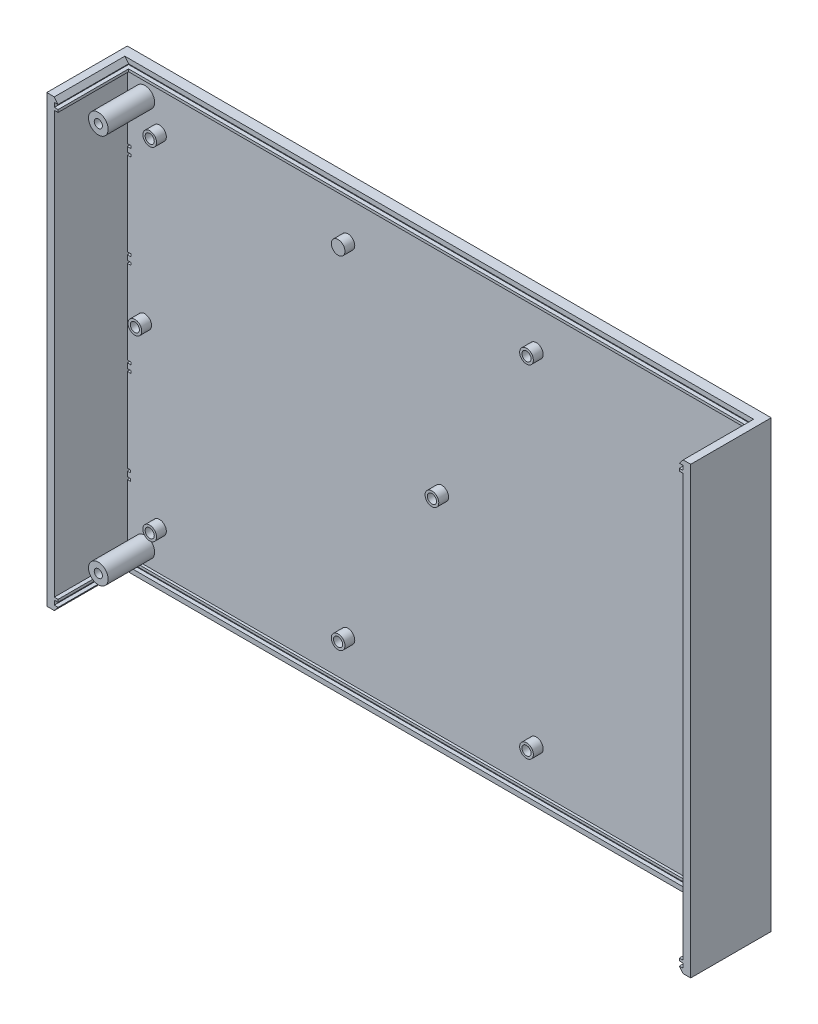
SolidWorks part; units mm, degrees
ref_plane "Front Plane" through (0, 0, 0) normal (0, 0, 1) x (1, 0, 0)
ref_plane "Top Plane" through (0, 0, 0) normal (0, 1, 0) x (1, 0, 0)
ref_plane "Right Plane" through (0, 0, 0) normal (1, 0, 0) x (0, 0, -1)
sketch "Sketch1" plane through (0, 0, 0) normal (0, 0, 1) x (1, 0, 0)
  line L0 (-127, 85.1535) -> (-127, -87.9475)
  line L81 (127, 85.1535) -> (127, -85.1535)
  line L83 (130.048, -89.8525) -> (130.048, 89.8525)
  line L86 (-127, 87.9475) -> (-127, 86.1695)
  line L87 (-130.048, 89.8525) -> (-130.048, -89.8525)
  line L88 (-127, -87.9475) -> (77.8375, -87.9475)
  line L89 (-127, -86.1695) -> (78.8702, -86.1695)
  line L90 (-127, -85.1535) -> (79.4604, -85.1535)
  line L91 (-130.048, -89.8525) -> (130.048, -89.8525)
  line L93 (-119.7257, 56.769) -> (-134.1956, 56.769) construction
  line L94 (-125.603, 58.7756) -> (-125.603, 57.7596)
  line L95 (-125.603, 54.7624) -> (-125.603, 55.7784)
  line L96 (-127, 58.7756) -> (-125.603, 58.7756)
  line L97 (-127, 57.7596) -> (-125.603, 57.7596)
  line L98 (-127, 55.7784) -> (-125.603, 55.7784)
  line L99 (-127, 54.7624) -> (-125.603, 54.7624)
  line L100 (127, -86.1695) -> (127, -87.9475)
  line L101 (77.8375, -87.9475) -> (127, -87.9475)
  line L102 (78.8702, -86.1695) -> (127, -86.1695)
  line L103 (79.4604, -85.1535) -> (127, -85.1535)
  line L104 (125.603, 58.7756) -> (125.603, 57.7596) construction
  line L105 (125.603, 54.7624) -> (125.603, 55.7784) construction
  line L106 (127, 58.7756) -> (125.603, 58.7756) construction
  line L107 (127, 57.7596) -> (125.603, 57.7596) construction
  line L108 (127, 55.7784) -> (125.603, 55.7784) construction
  line L109 (127, 54.7624) -> (125.603, 54.7624) construction
  line L110 (79.0715, 85.1535) -> (-127, 85.1535)
  line L111 (78.336, 86.1695) -> (-127, 86.1695)
  line L112 (77.0488, 87.9475) -> (-127, 87.9475)
  line L113 (130.048, 89.8525) -> (-130.048, 89.8525)
  line L115 (127, 87.9475) -> (77.0488, 87.9475)
  line L116 (127, 86.1695) -> (78.336, 86.1695)
  line L117 (127, 85.1535) -> (79.0715, 85.1535)
  line L118 (127, 87.9475) -> (127, 86.1695)
  line L119 (-119.7257, 18.923) -> (-134.1956, 18.923) construction
  line L120 (-125.603, 16.9164) -> (-125.603, 17.9324)
  line L121 (-127, 17.9324) -> (-125.603, 17.9324)
  line L122 (-127, 16.9164) -> (-125.603, 16.9164)
  line L123 (-127, 19.9136) -> (-125.603, 19.9136)
  line L124 (-127, 20.9296) -> (-125.603, 20.9296)
  line L125 (-125.603, 20.9296) -> (-125.603, 19.9136)
  line L126 (125.603, 16.9164) -> (125.603, 17.9324) construction
  line L127 (127, 17.9324) -> (125.603, 17.9324) construction
  line L128 (127, 16.9164) -> (125.603, 16.9164) construction
  line L129 (127, 19.9136) -> (125.603, 19.9136) construction
  line L130 (127, 20.9296) -> (125.603, 20.9296) construction
  line L131 (125.603, 20.9296) -> (125.603, 19.9136) construction
  line L132 (-119.7257, -18.923) -> (-134.1956, -18.923) construction
  line L133 (-125.603, -20.9296) -> (-125.603, -19.9136)
  line L134 (-127, -19.9136) -> (-125.603, -19.9136)
  line L135 (-127, -20.9296) -> (-125.603, -20.9296)
  line L136 (-127, -17.9324) -> (-125.603, -17.9324)
  line L137 (-127, -16.9164) -> (-125.603, -16.9164)
  line L138 (-125.603, -16.9164) -> (-125.603, -17.9324)
  line L139 (125.603, -20.9296) -> (125.603, -19.9136) construction
  line L140 (127, -19.9136) -> (125.603, -19.9136) construction
  line L141 (127, -20.9296) -> (125.603, -20.9296) construction
  line L142 (127, -17.9324) -> (125.603, -17.9324) construction
  line L143 (127, -16.9164) -> (125.603, -16.9164) construction
  line L144 (125.603, -16.9164) -> (125.603, -17.9324) construction
  line L145 (-119.7257, -56.769) -> (-134.1956, -56.769) construction
  line L146 (-125.6284, -58.7756) -> (-125.6284, -57.7596)
  line L147 (-127.0254, -57.7596) -> (-125.6284, -57.7596)
  line L148 (-127.0254, -58.7756) -> (-125.6284, -58.7756)
  line L149 (-127.0254, -55.7784) -> (-125.6284, -55.7784)
  line L150 (-127.0254, -54.7624) -> (-125.6284, -54.7624)
  line L151 (-125.6284, -54.7624) -> (-125.6284, -55.7784)
  line L152 (125.603, -58.7756) -> (125.603, -57.7596) construction
  line L153 (127, -57.7596) -> (125.603, -57.7596) construction
  line L154 (127, -58.7756) -> (125.603, -58.7756) construction
  line L155 (127, -55.7784) -> (125.603, -55.7784) construction
  line L156 (127, -54.7624) -> (125.603, -54.7624) construction
  line L157 (125.603, -54.7624) -> (125.603, -55.7784) construction
  line L158 (127, -89.8525) -> (125.476, -87.9475)
  line L159 (125.476, -86.1695) -> (125.476, -85.1535)
  line L160 (-127, -89.8525) -> (-125.476, -87.9475)
  line L161 (-125.476, -86.1695) -> (-125.476, -85.1535)
  line L162 (125.476, 86.1695) -> (125.476, 85.1535)
  line L163 (127, 89.8525) -> (125.476, 87.9475)
  line L164 (-127, 89.8525) -> (-125.476, 87.9475)
  line L165 (-125.476, 86.1695) -> (-125.476, 85.1535)
  circle A0 centre (-119.9134, -78.6765) radius 3.9624
  circle A1 centre (-113.9952, -68.9864) radius 2.7686
  circle A2 centre (-113.9952, -68.9864) radius 1.143
  circle A3 centre (-113.9952, -68.9864) radius 1.8415
  circle A4 centre (-119.9134, -78.6765) radius 1.651
  circle A5 centre (119.9134, -78.6765) radius 1.651 construction
  circle A6 centre (119.9134, -78.6765) radius 3.9624 construction
  circle A7 centre (-119.9134, 78.6765) radius 3.9624
  circle A8 centre (-119.9134, 78.6765) radius 1.651
  circle A9 centre (119.9134, 78.6765) radius 3.9624 construction
  circle A10 centre (119.9134, 78.6765) radius 1.651 construction
  circle A11 centre (0, 0) radius 2.7686
  circle A12 centre (0, 0) radius 1.8415
  circle A13 centre (0, 0) radius 1.143
  circle A14 centre (-113.9952, 68.9864) radius 1.8415
  circle A15 centre (-113.9952, 68.9864) radius 2.7686
  circle A16 centre (-113.9952, 68.9864) radius 1.143
  circle A17 centre (-37.8968, -68.9864) radius 1.8415
  circle A18 centre (-37.8968, -68.9864) radius 2.7686
  circle A19 centre (-37.8968, -68.9864) radius 1.143
  circle A20 centre (-37.8968, 68.9864) radius 2.7686
  circle A21 centre (-37.8968, 68.9864) radius 1.8415
  circle A22 centre (-37.8968, 68.9864) radius 1.143
  circle A23 centre (38.2016, -68.9864) radius 1.8415
  circle A24 centre (38.2016, -68.9864) radius 2.7686
  circle A25 centre (38.2016, -68.9864) radius 1.143
  circle A26 centre (38.2016, 68.9864) radius 2.7686
  circle A27 centre (38.2016, 68.9864) radius 1.8415
  circle A28 centre (38.2016, 68.9864) radius 1.143
  circle A29 centre (114.3, -68.9864) radius 1.8415 construction
  circle A30 centre (114.3, -68.9864) radius 2.7686 construction
  circle A31 centre (114.3, -68.9864) radius 1.143 construction
  circle A32 centre (114.3, 68.9864) radius 2.7686 construction
  circle A33 centre (114.3, 68.9864) radius 1.8415 construction
  circle A34 centre (114.3, 68.9864) radius 1.143 construction
  circle A35 centre (-119.9896, 0) radius 1.143
  circle A36 centre (-119.9896, 0) radius 1.8415
  circle A37 centre (-119.9896, 0) radius 2.7686
  circle A38 centre (119.9896, 0) radius 1.143 construction
  circle A39 centre (119.9896, 0) radius 1.8415 construction
  circle A40 centre (119.9896, 0) radius 2.7686 construction
  dimension "D1" = 2.286
  dimension "D2" = 3.683
  dimension "D3" = 5.5372
  dimension "D4" = 3.302
  dimension "D5" = 7.9248
  dimension "D6" = 38.2016
  dimension "D7" = 77.0488
  dimension "D8" = 77.8375
  dimension "D9" = 78.336
  dimension "D10" = 78.8702
  dimension "D11" = 79.0715
  dimension "D12" = 79.4604
  dimension "D13" = 114.3
  dimension "D14" = 119.9134
  dimension "D15" = 119.9896
  dimension "D16" = 125.476
  dimension "D17" = 125.603
  dimension "D18" = 127
  dimension "D19" = 85.1535
  dimension "D20" = 130.048
  dimension "D21" = 37.8968
  dimension "D22" = 113.9952
  dimension "D23" = 119.7257
  dimension "D24" = 119.9134
  dimension "D25" = 119.9896
  dimension "D26" = 125.476
  dimension "D27" = 125.6284
  dimension "D28" = 85.1535
  dimension "D29" = 89.8525
  dimension "D31" = 130.048
  dimension "D32" = 134.1956
  dimension "D33" = 16.9164
  dimension "D34" = 17.9324
  dimension "D35" = 18.923
  dimension "D36" = 19.9136
  dimension "D37" = 54.7624
  dimension "D38" = 57.7596
  dimension "D40" = 56.769
  dimension "D41" = 87.9475
  dimension "D42" = 16.9164
  dimension "D43" = 68.9864
  dimension "D44" = 78.6765
  dimension "D45" = 19.9136
  dimension "D46" = 54.7624
  dimension "D47" = 57.7596
  dimension "D50" = 179.705
  dimension "D52" = 18.923
  dimension "D57" = 56.769
  dimension "D60" = 68.9864
  dimension "D61" = 78.6765
extrude "Boss-Extrude1" add sketch "Sketch1" along normal blind 3.048 contours L165 L111 L86 L112 L164 L113 L87 L91 L160 L88 L0 L110 | L113 L164 L112 L115 L163 | L111 L165 L110 L117 L162 L116 | L118 L115 L112 L86 L111 L116 | L113 L163 L115 L118 L116 L162 L117 L81 L103 L159 L102 L100 L101 L158 L91 L83 | L161 L89 L102 L159 L103 L90 | L102 L89 L0 L88 L101 L100 | L160 L91 L158 L101 L88 | L150 L151 L149 L0 L147 L146 L148 L90 L103 L81 L117 L110 L96 L94 L97 L98 L95 L99 L124 L125 L123 L121 L120 L122 L137 L138 L136 L134 L133 L135 A37 A26 A24 A20 | A20 A21 | A24 A23 | A25 | A23 A25 | A19 | A17 A19 | A18 A17 | A0 A4 | A4 | A1 A3 | A2 | A37 A36 | A36 A35 | A35 | A7 A8 | A15 A14 | A14 A16 | A16 | A28 | A27 A28 | A26 A27 | A11 A12 | A12 A13 | A13 | L90 L103 L81 L117 L110 L0 L88 L101 L100 L102 L89 | A21 | A2 | A3 | A8 region at (-126.238, 82.0954, 0) region at (-128.5069, 0.2402, 0) region at (0, 85.6615, 0) region at (0, 87.0585, 0) region at (128.5006, 0, 0) region at (0, 88.9019, 0) region at (0, -85.6615, 0) region at (0, -87.0585, 0) region at (0, -88.9019, 0) region at (-123.7637, -78.6765, 0) region at (-116.6855, -68.9864, 0) region at (-113.9952, -68.9864, 0) region at (-119.9134, -78.6765, 0) region at (-123.7637, 78.6765, 0) region at (-2.6903, 0, 0) region at (-1.7894, 0, 0) region at (0, 0, 0) region at (-115.7846, 68.9864, 0) region at (-116.6855, 68.9864, 0) region at (-113.9952, 68.9864, 0) region at (-39.6862, -68.9864, 0) region at (-40.5871, -68.9864, 0) region at (-37.8968, -68.9864, 0) region at (-40.5871, 68.9864, 0) region at (36.4122, -68.9864, 0) region at (35.5113, -68.9864, 0) region at (38.2016, -68.9864, 0) region at (35.5113, 68.9864, 0) region at (36.4122, 68.9864, 0) region at (38.2016, 68.9864, 0) region at (-119.9896, 0, 0) region at (-121.779, 0, 0) region at (-122.6799, 0, 0)
extrude "Boss-Extrude2" add sketch "Sketch1<5>" along normal blind 32.5374 contours L165 L111 L86 L112 L164 L113 L87 L91 L160 L88 L0 L110 | L89 L161 L90 L0 | L113 L163 L115 L118 L116 L162 L117 L81 L103 L159 L102 L100 L101 L158 L91 L83 region at (-128.5069, 0.2402, 0) region at (128.5006, 0, 0) region at (-126.238, -85.6615, 0)
sketch "Sketch1<5>" plane through (0, 0, 0) normal (0, 0, 1) x (1, 0, 0) same geometry as "Sketch1"
extrude "Boss-Extrude3" add sketch "Sketch1<6>" along normal blind 7.0104 contours A1 A3 | A18 A17 | A26 A27 | A11 A12 | A24 A23 | A15 A14 | A37 A36 | A20 region at (-116.6855, -68.9864, 0) region at (-2.6903, 0, 0) region at (-116.6855, 68.9864, 0) region at (-40.5871, -68.9864, 0) region at (35.5113, -68.9864, 0) region at (35.5113, 68.9864, 0) region at (-122.6799, 0, 0)
sketch "Sketch1<6>" plane through (0, 0, 0) normal (0, 0, 1) x (1, 0, 0) same geometry as "Sketch1"
extrude "Boss-Extrude4" add sketch "Sketch1<7>" along normal blind 4.064 contours L161 L89 L102 L159 L103 L90 | L160 L91 L158 L101 L88 | L113 L164 L112 L115 L163 | L111 L165 L110 L117 L162 L116 region at (0, 85.6615, 0) region at (0, 88.9019, 0) region at (0, -85.6615, 0) region at (0, -88.9019, 0)
sketch "Sketch1<7>" plane through (0, 0, 0) normal (0, 0, 1) x (1, 0, 0) same geometry as "Sketch1"
extrude "Boss-Extrude5" add sketch "Sketch1<8>" along normal blind 21.844 contours A0 A4 | A7 A8 region at (-123.7637, -78.6765, 0) region at (-123.7637, 78.6765, 0)
sketch "Sketch1<8>" plane through (0, 0, 0) normal (0, 0, 1) x (1, 0, 0) same geometry as "Sketch1"
sketch "Sketch3" plane through (0, 0, 3.048) normal (0, 0, 1) x (1, 0, 0)
  line L0 (-127, 86.1695) -> (127, 86.1695) construction
  line L1 (127, 86.1695) -> (127, 87.9475) construction
  line L2 (127, 87.9475) -> (-127, 87.9475) construction
  line L3 (-127, 87.9475) -> (-127, 86.1695) construction
  line L4 (-127, -87.9475) -> (127, -87.9475) construction
  line L5 (127, -87.9475) -> (127, -86.1695) construction
  line L6 (127, -86.1695) -> (-127, -86.1695) construction
  line L7 (-127, -86.1695) -> (-127, -87.9475) construction
  line L8 (-127, 86.1695) -> (127, 86.1695)
  line L9 (127, 86.1695) -> (127, 87.9475)
  line L10 (127, 87.9475) -> (-127, 87.9475)
  line L11 (-127, 87.9475) -> (-127, 86.1695)
  line L12 (-127, -87.9475) -> (127, -87.9475)
  line L13 (127, -87.9475) -> (127, -86.1695)
  line L14 (127, -86.1695) -> (-127, -86.1695)
  line L15 (-127, -86.1695) -> (-127, -87.9475)
extrude "Cut-Extrude1" cut sketch "Sketch3" against normal blind 0.508
